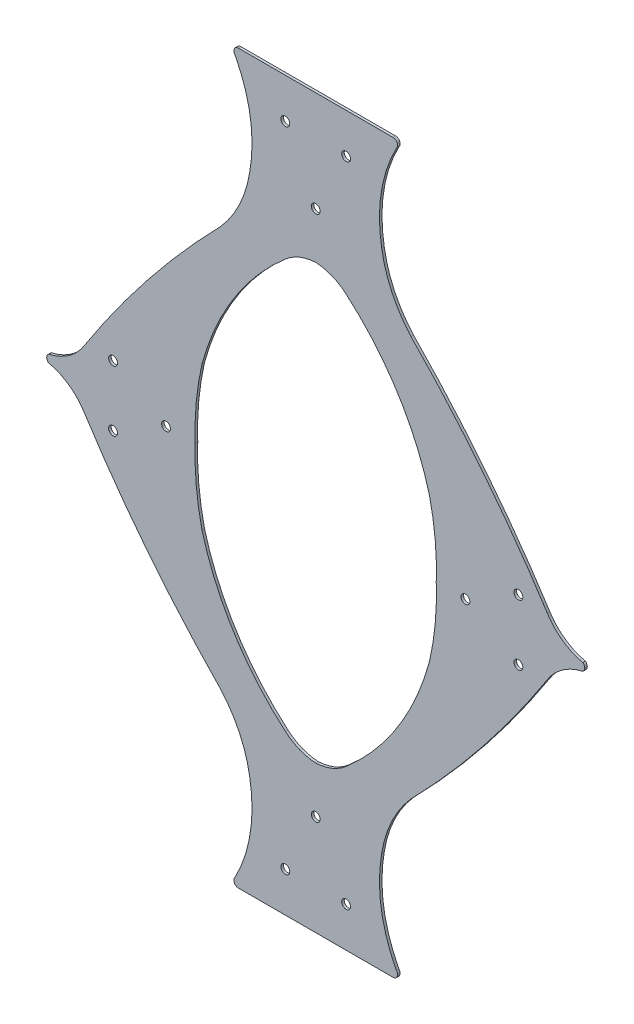
SolidWorks part; units mm, degrees
ref_plane "Front Plane" through (0, 0, 0) normal (0, 0, 1) x (1, 0, 0)
ref_plane "Top Plane" through (0, 0, 0) normal (0, 1, 0) x (1, 0, 0)
ref_plane "Right Plane" through (0, 0, 0) normal (1, 0, 0) x (0, 0, -1)
sketch "Model" plane through (0, 0, 0) normal (0, 0, 1) x (1, 0, 0)
  line B0 (-376.3936, 0) -> (376.3936, 0) construction
  line B1 (0, 914.4) -> (-194.4798, 914.4)
  line B2 (0, 914.4) -> (194.4798, 914.4)
  line B3 (0, -914.4) -> (-194.4798, -914.4)
  line B4 (0, -914.4) -> (194.4798, -914.4)
  arc B5 (-194.4798, 914.4) -> (-202.9832, 895.3321) centre (-194.4798, 902.97) ccw
  arc B6 (-165.9389, 658.1298) -> (-202.9832, 895.3321) centre (-527.5496, 723.1502) ccw
  arc B7 (-239.6834, 503.1053) -> (-165.9389, 658.1298) centre (-465.825, 705.7322) ccw
  arc B8 (-239.6834, 503.1053) -> (-582.0374, 72.7477) centre (1699.953, -1391.2476) ccw
  arc B9 (-671.3071, 9.5736) -> (-582.0374, 72.7477) centre (-702.2766, 147.9952) ccw
  arc B10 (-671.3071, 9.5736) -> (-676.2743, 0) centre (-664.8452, 0.1455) ccw
  arc B11 (-76.1318, 514.3055) -> (-285.9807, 180.6809) centre (360.5192, 6.8439) ccw
  arc B12 (0, 545.0832) -> (-76.1318, 514.3055) centre (7, 418.2194) ccw
  arc B13 (-285.9807, 180.6809) -> (-302.956, 0) centre (389.9953, 26.0335) ccw
  circle B14 centre (0, 661.9875) radius 11.1125
  circle B15 centre (-76.3912, 814.1372) radius 11.1125
  circle B16 centre (-376.3936, 0) radius 11.1125
  circle B17 centre (-509.4933, 76.235) radius 11.1125
  arc B18 (202.9832, 895.3321) -> (194.4798, 914.4) centre (194.4798, 902.97) ccw
  arc B19 (202.9832, 895.3321) -> (165.9389, 658.1298) centre (527.5496, 723.1502) ccw
  arc B20 (165.9389, 658.1298) -> (239.6834, 503.1053) centre (465.825, 705.7322) ccw
  arc B21 (582.0374, 72.7477) -> (239.6834, 503.1053) centre (-1699.953, -1391.2476) ccw
  arc B22 (582.0374, 72.7477) -> (671.3071, 9.5736) centre (702.2766, 147.9952) ccw
  arc B23 (676.2743, 0) -> (671.3071, 9.5736) centre (664.8452, 0.1455) ccw
  arc B24 (285.9807, 180.6809) -> (76.1318, 514.3055) centre (-360.5192, 6.8439) ccw
  arc B25 (76.1318, 514.3055) -> (0, 545.0832) centre (-7, 418.2194) ccw
  arc B26 (302.956, 0) -> (285.9807, 180.6809) centre (-389.9953, 26.0335) ccw
  circle B27 centre (76.3912, 814.1372) radius 11.1125
  circle B28 centre (376.3936, 0) radius 11.1125
  circle B29 centre (509.4933, 76.235) radius 11.1125
  arc B30 (-202.9832, -895.3321) -> (-194.4798, -914.4) centre (-194.4798, -902.97) ccw
  arc B31 (-202.9832, -895.3321) -> (-165.9389, -658.1298) centre (-527.5496, -723.1502) ccw
  arc B32 (-165.9389, -658.1298) -> (-239.6834, -503.1053) centre (-465.825, -705.7322) ccw
  arc B33 (-582.0374, -72.7477) -> (-239.6834, -503.1053) centre (1699.953, 1391.2476) ccw
  arc B34 (-582.0374, -72.7477) -> (-671.3071, -9.5736) centre (-702.2766, -147.9952) ccw
  arc B35 (-676.2743, 0) -> (-671.3071, -9.5736) centre (-664.8452, -0.1455) ccw
  arc B36 (-285.9807, -180.6809) -> (-76.1318, -514.3055) centre (360.5192, -6.8439) ccw
  arc B37 (-76.1318, -514.3055) -> (0, -545.0832) centre (7, -418.2194) ccw
  arc B38 (-302.956, 0) -> (-285.9807, -180.6809) centre (389.9953, -26.0335) ccw
  circle B39 centre (0, -661.9875) radius 11.1125
  circle B40 centre (-76.3912, -814.1372) radius 11.1125
  circle B41 centre (-509.4933, -76.235) radius 11.1125
  arc B42 (194.4798, -914.4) -> (202.9832, -895.3321) centre (194.4798, -902.97) ccw
  arc B43 (165.9389, -658.1298) -> (202.9832, -895.3321) centre (527.5496, -723.1502) ccw
  arc B44 (239.6834, -503.1053) -> (165.9389, -658.1298) centre (465.825, -705.7322) ccw
  arc B45 (239.6834, -503.1053) -> (582.0374, -72.7477) centre (-1699.953, 1391.2476) ccw
  arc B46 (671.3071, -9.5736) -> (582.0374, -72.7477) centre (702.2766, -147.9952) ccw
  arc B47 (671.3071, -9.5736) -> (676.2743, 0) centre (664.8452, -0.1455) ccw
  arc B48 (76.1318, -514.3055) -> (285.9807, -180.6809) centre (-360.5192, -6.8439) ccw
  arc B49 (0, -545.0832) -> (76.1318, -514.3055) centre (-7, -418.2194) ccw
  arc B50 (285.9807, -180.6809) -> (302.956, 0) centre (-389.9953, -26.0335) ccw
  circle B51 centre (76.3912, -814.1372) radius 11.1125
  circle B52 centre (509.4933, -76.235) radius 11.1125
sketch_block_instance "Block2-1"
sketch_block "Block2"
extrude "Boss-Extrude1" add sketch "Model" along normal blind 6.35 contours B46 B47 B23 B22 B21 B20 B19 B18 B2 B1 B5 B6 B7 B8 B9 B10 B35 B34 B33 B32 B31 B30 B3 B4 B42 B43 B44 B45 B52 B51 B50 B48 B49 B37 B36 B38 B13 B11 B12 B25 B24 B26 B14 B15 B16 region at (97.2399, 891.6538, 0)
